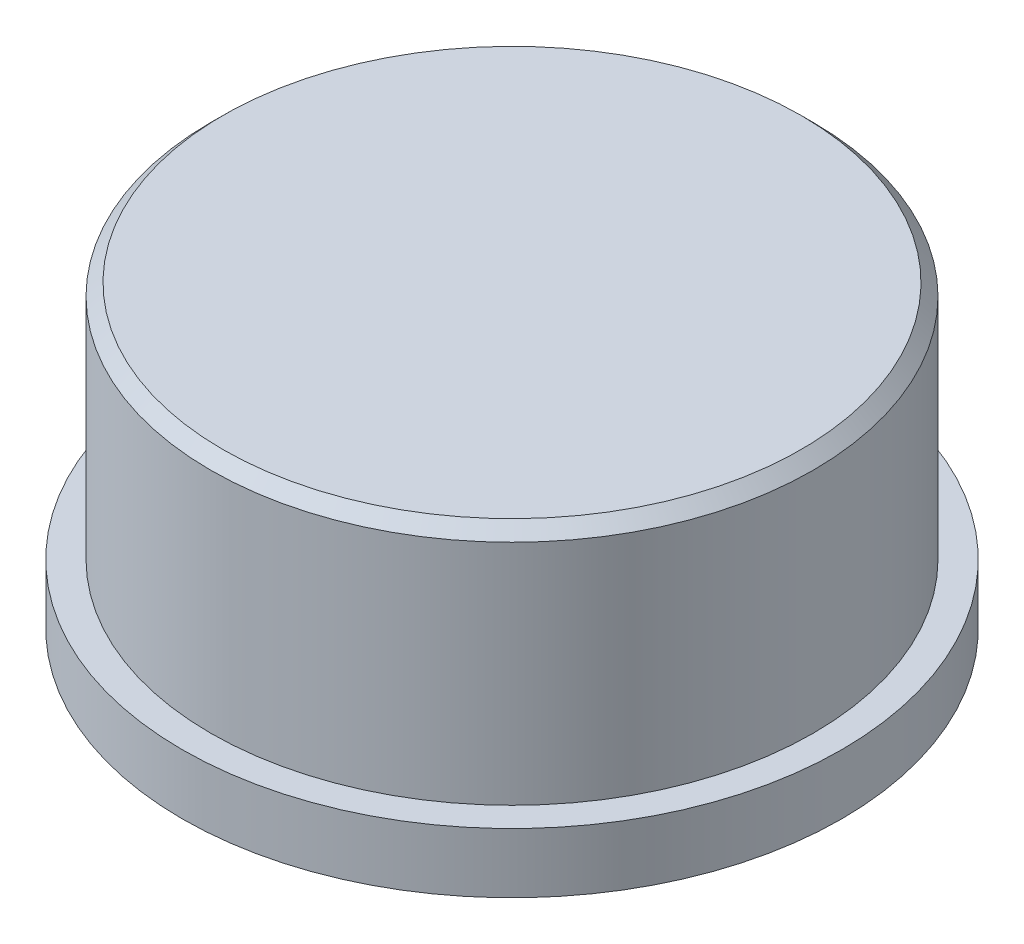
SolidWorks part; units mm, degrees
material "ABS"
ref_plane "Front Plane" through (0, 0, 0) normal (0, 0, 1) x (1, 0, 0)
ref_plane "Top Plane" through (0, 0, 0) normal (0, 1, 0) x (1, 0, 0)
ref_plane "Right Plane" through (0, 0, 0) normal (1, 0, 0) x (0, 0, -1)
sketch "Sketch1" plane through (0, 0, 0) normal (0, 1, 0) x (1, 0, 0)
  circle A0 centre (0, 0) radius 5.5
  dimension "D1" = 11
extrude "Boss-Extrude1" add sketch "Sketch1" along normal blind 1
sketch "Sketch2" plane through (0, 1, 0) normal (0, 1, 0) x (1, 0, 0)
  circle A0 centre (0, 0) radius 5.025
  dimension "D1" = 10.05
extrude "Boss-Extrude2" add sketch "Sketch2" along normal blind 4
sketch "Sketch3" plane through (0, 0, 0) normal (0, -1, 0) x (1, 0, 0)
  line L1 (3.0022, 0) -> (1.5011, 2.6)
  line L2 (1.5011, 2.6) -> (-1.5011, 2.6)
  line L3 (-1.5011, 2.6) -> (-3.0022, 0)
  line L4 (-3.0022, 0) -> (-1.5011, -2.6)
  line L5 (-1.5011, -2.6) -> (1.5011, -2.6)
  line L6 (1.5011, -2.6) -> (3.0022, 0)
  circle A0 centre (0, 0) radius 2.6 construction
  dimension "D1" = 5.2
extrude "Cut-Extrude1" cut sketch "Sketch3" against normal blind 4 contours L1 L2 L3 L4 L5 L6
chamfer "Chamfer1" distance 0.2 angle 45 1 edges at (0, 5, 5.025)
